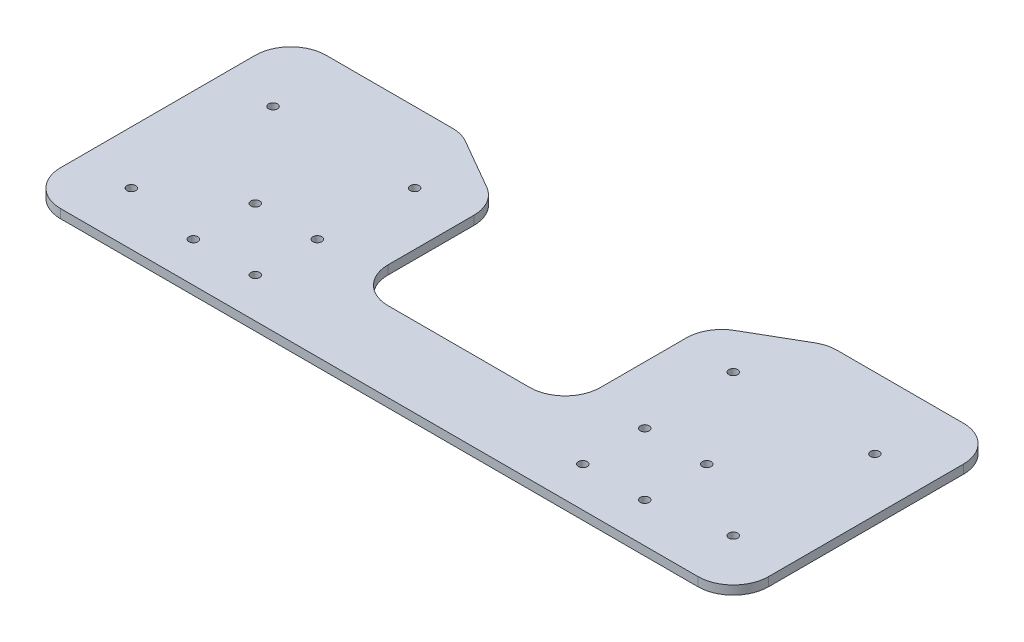
SolidWorks part; units mm, degrees
ref_plane "前视基准面" through (0, 0, 0) normal (0, 0, 1) x (1, 0, 0)
ref_plane "上视基准面" through (0, 0, 0) normal (0, 1, 0) x (1, 0, 0)
ref_plane "右视基准面" through (0, 0, 0) normal (1, 0, 0) x (0, 0, -1)
sketch "草图1" plane through (0, 0, 0) normal (0, 1, 0) x (1, 0, 0)
  line L0 (0, 0) -> (-180, 0)
  line L1 (-200, 20) -> (-200, 130)
  line L2 (-180, 150) -> (-108.6603, 150)
  line L3 (-98.6603, 147.3205) -> (-70, 130.7735)
  line L4 (-60, 113.453) -> (-60, 65)
  line L5 (-40, 45) -> (0, 45)
  line L6 (0, 45) -> (0, 0)
  line L8 (-127.5, 22.5) -> (-92.5, 22.5) construction
  line L9 (-127.5, 22.5) -> (-127.5, 57.5) construction
  line L10 (-127.5, 57.5) -> (-92.5, 57.5) construction
  line L11 (-92.5, 22.5) -> (-92.5, 57.5) construction
  line L12 (-127.5, 22.5) -> (-92.5, 57.5) construction
  line L13 (-127.5, 57.5) -> (-92.5, 22.5) construction
  arc A0 (-60, 65) -> (-40, 45) centre (-40, 65) ccw
  arc A1 (-180, 0) -> (-200, 20) centre (-180, 20) cw
  arc A2 (-200, 130) -> (-180, 150) centre (-180, 130) cw
  arc A3 (-108.6603, 150) -> (-98.6603, 147.3205) centre (-108.6603, 130) cw
  arc A4 (-70, 130.7735) -> (-60, 113.453) centre (-80, 113.453) cw
  circle A5 centre (-127.5, 57.5) radius 2.5
  circle A6 centre (-92.5, 57.5) radius 2.5
  circle A7 centre (-127.5, 22.5) radius 2.5
  circle A8 centre (-92.5, 22.5) radius 2.5
  circle A9 centre (-170, 110) radius 2.5
  circle A10 centre (-90, 110) radius 2.5
  circle A11 centre (-170, 30) radius 2.5
  point P10 (-60, 45)
  point P13 (-200, 0)
  point P16 (-200, 150)
  point P21 (-60, 125)
  point P22 (-110, 40)
  point P38 (-92.5, 57.5)
  point P39 (-127.5, 22.5)
  point P40 (-127.5, 57.5)
  point P41 (-92.5, 22.5)
  dimension "D7" = 20
  dimension "D8" = 20
  dimension "D9" = 20
  dimension "D11" = 5
  dimension "D12" = 5
  dimension "D13" = 5
  dimension "D14" = 5
  dimension "D17" = 5
  dimension "D18" = 5
  dimension "D19" = 5
  dimension "D1" = 200
  dimension "D2" = 150
  dimension "D3" = 150
  dimension "D4" = 60
  dimension "D5" = 45
  dimension "D6" = 80
  dimension "D10" = 35
  dimension "D15" = 40
  dimension "D16" = 50
  dimension "D20" = 80
  dimension "D21" = 80
  dimension "D22" = 40
  dimension "D23" = 30
extrude "凸台-拉伸1" add sketch "草图1" along normal blind 5
sketch "草图2" plane through (0, 0, 0) normal (0, 1, 0) x (1, 0, 0)
  line L0 (-60, 65) -> (-60, 113.453) construction
  line L1 (-135, 65) -> (-85, 65)
  line L2 (-135, 65) -> (-135, 15)
  line L3 (-135, 15) -> (-85, 15)
  line L4 (-85, 65) -> (-85, 15)
  line L5 (-135, 65) -> (-85, 15) construction
  line L6 (-135, 15) -> (-85, 65) construction
  line L7 (-180, 0) -> (0, 0) construction
  point P0 (-110, 40)
  dimension "D1" = 50
  dimension "D2" = 50
  dimension "D3" = 50
  dimension "D4" = 40
extrude "凸台-拉伸2" add sketch "草图2" against normal blind 11.5
sketch "草图3" plane through (-135, 0, 0) normal (-1, 0, 0) x (0, 0, 1)
  line L0 (-65, -11.5) -> (-15, -11.5) construction
  circle A0 centre (-40, -11.5) radius 11.5
  dimension "D1" = 23
extrude "切除-拉伸1" cut sketch "草图3" against normal through all
extrude "切除-拉伸3" cut sketch "草图1<7>" against normal through all contours A5 | A6 | A7 | A8 region at (-127.5, 0, -57.5) region at (-92.5, 0, -57.5) region at (-127.5, 0, -22.5) region at (-92.5, 0, -22.5)
sketch "草图1<7>" plane through (0, 0, 0) normal (0, 1, 0) x (1, 0, 0) same geometry as "草图1"
mirror "镜向1" about plane through (0, 5, -45) normal (-1, 0, 0) of "切除-拉伸3", "切除-拉伸1", "凸台-拉伸2", "凸台-拉伸1"
